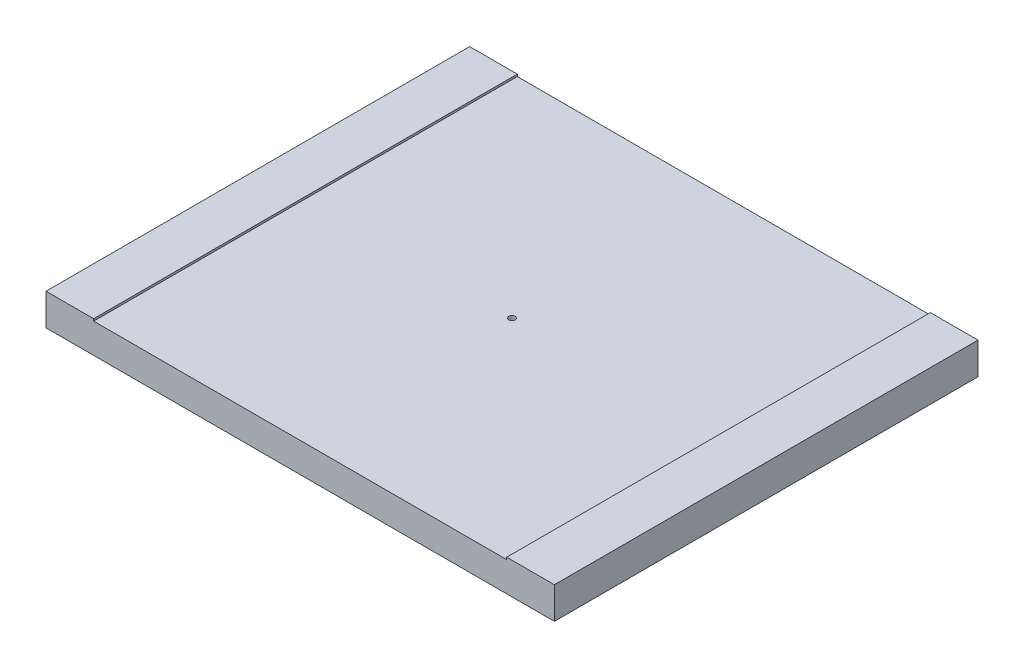
SolidWorks part; units mm, degrees
ref_plane "Front Plane" through (0, 0, 0) normal (0, 0, 1) x (1, 0, 0)
ref_plane "Top Plane" through (0, 0, 0) normal (0, 1, 0) x (1, 0, 0)
ref_plane "Right Plane" through (0, 0, 0) normal (1, 0, 0) x (0, 0, -1)
sketch "Sketch1" plane through (0, 0, 0) normal (0, 1, 0) x (1, 0, 0)
  line L1 (-120, -100) -> (120, -100)
  line L2 (-120, -100) -> (-120, 100)
  line L3 (-120, 100) -> (120, 100)
  line L4 (120, -100) -> (120, 100)
  line L5 (-120, -100) -> (120, 100) construction
  line L6 (-120, 100) -> (120, -100) construction
  point P0 (0, 0)
  dimension "D1" = 240
  dimension "D2" = 200
extrude "Boss-Extrude1" add sketch "Sketch1" along normal mid plane 15
sketch "Sketch2" plane through (0, 7.5, 0) normal (0, 1, 0) x (1, 0, 0)
  circle A0 centre (0, 0) radius 1.5
  dimension "D1" = 3
extrude "Cut-Extrude1" cut sketch "Sketch2" against normal through all
sketch "Sketch3" plane through (0, 7.5, 0) normal (0, 1, 0) x (1, 0, 0)
  line L1 (-92.5, -105) -> (92.5, -105)
  line L2 (-97.5, -100) -> (-97.5, 100)
  line L3 (-92.5, 105) -> (92.5, 105)
  line L4 (97.5, -100) -> (97.5, 100)
  line L5 (-97.5, -105) -> (97.5, 105) construction
  line L6 (-97.5, 105) -> (97.5, -105) construction
  arc A0 (-92.5, -105) -> (-97.5, -100) centre (-92.5, -100) cw
  arc A1 (97.5, -100) -> (92.5, -105) centre (92.5, -100) cw
  arc A2 (97.5, 100) -> (92.5, 105) centre (92.5, 100) ccw
  arc A3 (-92.5, 105) -> (-97.5, 100) centre (-92.5, 100) ccw
  point P0 (0, 0)
  dimension "D3" = 5
  dimension "D1" = 195
  dimension "D2" = 210
extrude "Cut-Extrude2" cut sketch "Sketch3" against normal blind 1
